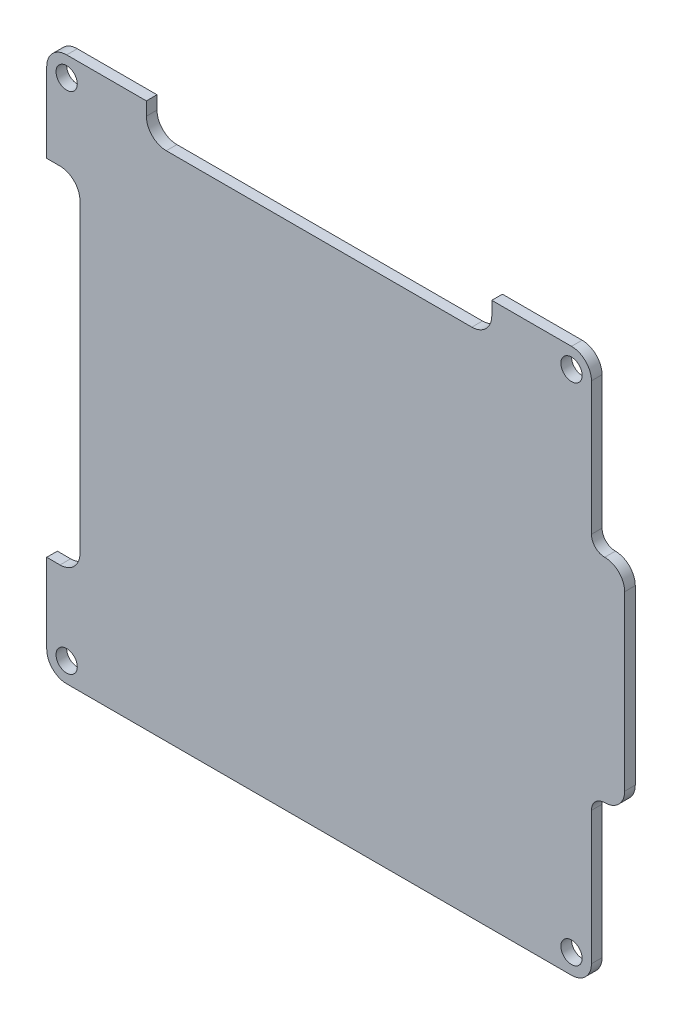
SolidWorks part; units mm, degrees
ref_plane "Front Plane" through (0, 0, 0) normal (0, 0, 1) x (1, 0, 0)
ref_plane "Top Plane" through (0, 0, 0) normal (0, 1, 0) x (1, 0, 0)
ref_plane "Right Plane" through (0, 0, 0) normal (1, 0, 0) x (0, 0, -1)
sketch "Sketch1" plane through (0, 0, 0) normal (0, 0, 1) x (1, 0, 0)
  line L0 (-15.5, 86.75) -> (-15.5, 81.75)
  line L1 (-0.5, 86.75) -> (-15.5, 86.75)
  line L2 (-0.5, 61.75) -> (4.5, 61.75)
  line L3 (4.5, 61.75) -> (4.5, 29.75)
  line L4 (-82.5, 86.75) -> (-82.5, 71.75)
  line L5 (-15.5, 81.75) -> (-67.5, 81.75)
  line L6 (-67.5, 81.75) -> (-67.5, 86.75)
  line L7 (4.5, 29.75) -> (-0.5, 29.75)
  line L8 (-0.5, 29.75) -> (-0.5, 4.75)
  line L14 (-0.5, 4.75) -> (-82.5, 4.75)
  line L17 (-82.5, 71.75) -> (-77.5, 71.75)
  line L18 (-77.5, 71.75) -> (-77.5, 19.75)
  line L19 (-77.5, 19.75) -> (-82.5, 19.75)
  line L20 (-67.5, 86.75) -> (-82.5, 86.75)
  line L22 (-82.5, 19.75) -> (-82.5, 4.75)
  line L23 (-0.5, 86.75) -> (-0.5, 61.75)
  dimension "D1" = 82
  dimension "D2" = 15
  dimension "D3" = 82
  dimension "D4" = 15
  dimension "D5" = 5
  dimension "D6" = 25
  dimension "D7" = 15
  dimension "D8" = 15
  dimension "D9" = 25
  dimension "D10" = 5
extrude "Boss-Extrude1" add sketch "Sketch1" against normal blind 1.6
hole_wizard "Ø3.2 (3.2) Diameter Hole1" positions "Sketch6" profile "Sketch5" hole size "Ø3.2" standard "Ansi Metric" end condition up to next
sketch "Sketch6" plane through (0, 0, -1.6) normal (0, 0, -1) x (-1, 0, 0)
  line L1 (0.5, 86.75) -> (15.5, 86.75) construction
  line L2 (67.5, 86.75) -> (82.5, 86.75) construction
  line L3 (82.5, 86.75) -> (82.5, 71.75) construction
  line L4 (82.5, 19.75) -> (82.5, 4.75) construction
  line L5 (82.5, 4.75) -> (0.5, 4.75) construction
  line L6 (0.5, 61.75) -> (0.5, 86.75) construction
  line L8 (82.5, 4.75) -> (0.5, 4.75) construction
  line L9 (0.5, 61.75) -> (0.5, 86.75) construction
  point P1 (3.5, 83.75)
  point P4 (3.5, 7.75)
  point P7 (79.5, 7.75)
  point P10 (79.5, 83.75)
  dimension "D1" = 3
  dimension "D2" = 3
  dimension "D3" = 3
  dimension "D4" = 3
  dimension "D5" = 3
  dimension "D6" = 3
  dimension "D7" = 3
  dimension "D8" = 3
sketch "Sketch5" plane through (-3.5, 83.75, -1.6) normal (1, 0, 0) x (0, 1, 0)
  line L0 (0, 0) -> (0, 1.6)
  line L1 (0, 1.6) -> (1.6, 1.6)
  line L2 (1.6, 1.6) -> (1.6, 0)
  line L5 (1.6, 0) -> (0, 0)
  line L11 (0, -6.35) -> (0, 107.95) construction
  dimension "Thru Hole Dia." = 3.2
  dimension "Thru Hole Depth" = 1.6
fillet "Fillet1" radius 3 10 edges at (-67.5, 81.75, -0.8) (-15.5, 81.75, -0.8) (-77.5, 71.75, -0.8) (-77.5, 19.75, -0.8) (-82.5, 86.75, -0.8) (-82.5, 4.75, -0.8) (-0.5, 86.75, -0.8) (-0.5, 4.75, -0.8) (4.5, 29.75, -0.8) (4.5, 61.75, -0.8)
fillet "Fillet3" radius 2 2 edges at (-0.5, 29.75, -0.8) (-0.5, 61.75, -0.8)
